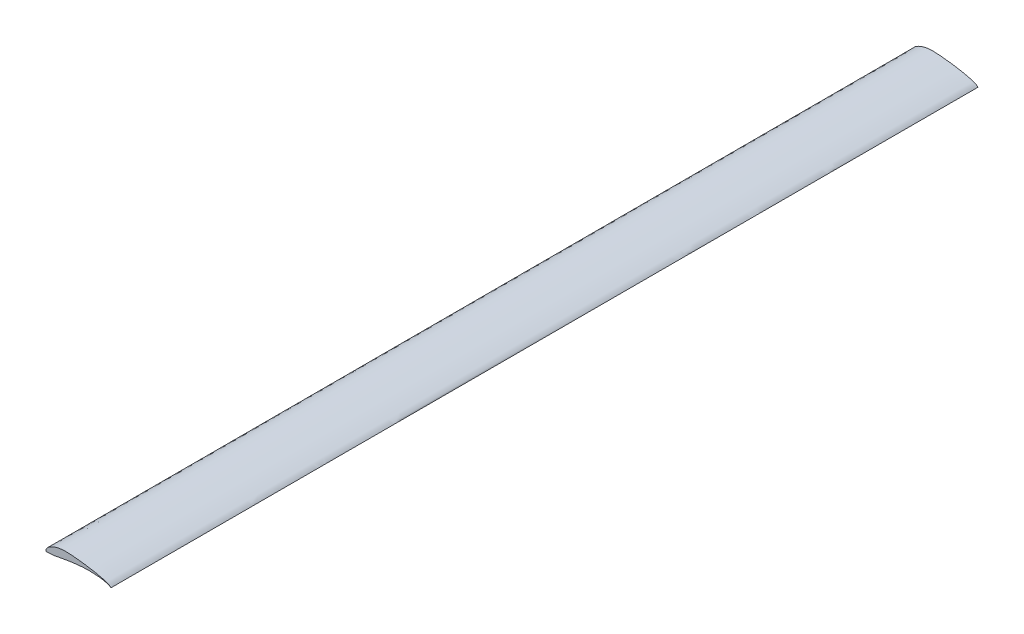
SolidWorks part; units mm, degrees
ref_plane "Front Plane" through (0, 0, 0) normal (0, 0, 1) x (1, 0, 0)
ref_plane "Top Plane" through (0, 0, 0) normal (0, 1, 0) x (1, 0, 0)
ref_plane "Right Plane" through (0, 0, 0) normal (1, 0, 0) x (0, 0, -1)
curve "Curve1"
  spline degree 3 poles (298.8391, 0.7791, 0) (300.272, -0.1937, 0) (299.0156, 0.7424, 0) (298.1815, 1.5608, 0) (296.3296, 3.2701, 0) (294.1447, 5.0885, 0) (291.156, 6.9216, 0) (287.4395, 8.6981, 0) (282.9528, 10.5521, 0) (277.7028, 12.4577, 0) (271.7139, 14.4016, 0) (265.0173, 16.3668, 0) (257.6504, 18.3442, 0) (249.6539, 20.3155, 0) (241.0736, 22.2665, 0) (231.9608, 24.185, 0) (222.371, 26.0611, 0) (212.3603, 27.8718, 0) (201.9917, 29.6144, 0) (191.325, 31.2666, 0) (180.4292, 32.8315, 0) (169.3741, 34.2968, 0) (158.2398, 35.6577, 0) (147.1152, 36.924, 0) (136.0925, 38.0635, 0) (125.2615, 39.0551, 0) (114.6983, 39.843, 0) (104.4633, 40.3849, 0) (94.6135, 40.6189, 0) (85.1993, 40.594, 0) (76.2382, 40.133, 0) (67.7268, 39.1989, 0) (59.6304, 37.8781, 0) (51.9471, 36.167, 0) (44.6848, 34.1605, 0) (37.8742, 31.8941, 0) (31.5442, 29.4209, 0) (25.7343, 26.754, 0) (20.4629, 23.9477, 0) (15.7589, 21.0338, 0) (11.6518, 18.0518, 0) (8.1431, 15.065, 0) (5.2838, 12.0407, 0) (3.0875, 9.0051, 0) (1.4651, 6.0519, 0) (0.4254, 3.2479, 0) (-0.0701, 0.6599, 0) (0.0255, -1.529, 0) (0.5891, -3.5365, 0) (2.6838, -4.5331, 0) (5.5002, -4.6729, 0) (9.3531, -4.8084, 0) (14.1983, -4.5995, 0) (19.9811, -4.2155, 0) (26.6372, -3.6005, 0) (34.0984, -2.7684, 0) (42.3284, -1.7012, 0) (51.3231, -0.2097, 0) (61.1264, 1.6605, 0) (71.7872, 3.696, 0) (83.2535, 5.8452, 0) (95.4531, 8.0188, 0) (108.2966, 10.1354, 0) (121.6843, 12.1242, 0) (135.5008, 13.9123, 0) (149.6219, 15.4476, 0) (163.9141, 16.6612, 0) (178.2341, 17.5215, 0) (192.4322, 17.9944, 0) (206.3544, 18.0542, 0) (219.8454, 17.6966, 0) (232.7507, 16.9302, 0) (244.9151, 15.7648, 0) (256.1938, 14.245, 0) (266.44, 12.4151, 0) (275.5335, 10.3363, 0) (283.3067, 8.1119, 0) (289.6683, 5.7379, 0) (294.2072, 3.5653, 0) (297.5535, 1.5564, 0) (298.8391, 0.7791, 0) (300.272, -0.1937, 0) (299.0156, 0.7424, 0) knots -0.009748 -0.004147 -0.001 0 0.00098 0.003649 0.007483 0.012095 0.017526 0.024052 0.031783 0.040678 0.05071 0.061833 0.073989 0.087118 0.101145 0.115991 0.13157 0.147788 0.164551 0.181758 0.199312 0.217095 0.23499 0.252857 0.270541 0.287887 0.304773 0.321101 0.336806 0.3518 0.366031 0.379616 0.392653 0.40517 0.417172 0.428604 0.439419 0.449597 0.459102 0.467908 0.475988 0.483309 0.489875 0.495803 0.501149 0.505903 0.510047 0.513579 0.516447 0.51935 0.523823 0.529974 0.537716 0.546968 0.557637 0.56962 0.582804 0.597247 0.613135 0.630444 0.649056 0.668822 0.689595 0.71119 0.733427 0.756094 0.778989 0.80189 0.824567 0.846792 0.868338 0.888978 0.908492 0.926659 0.943286 0.958169 0.971136 0.981956 0.990252 0.995853 0.999 1 1.00098 1.003649 1.007483 periodic
sketch "Sketch2" plane through (0, 0, 0) normal (0, 0, 1) x (1, 0, 0)
  spline S0 degree 3 poles (298.8391, 0.7791) (300.272, -0.1937) (299.0156, 0.7424) (298.1815, 1.5608) (296.3296, 3.2701) (294.1447, 5.0885) (291.156, 6.9216) (287.4395, 8.6981) (282.9528, 10.5521) (277.7028, 12.4577) (271.7139, 14.4016) (265.0173, 16.3668) (257.6504, 18.3442) (249.6539, 20.3155) (241.0736, 22.2665) (231.9608, 24.185) (222.371, 26.0611) (212.3603, 27.8718) (201.9917, 29.6144) (191.325, 31.2666) (180.4292, 32.8315) (169.3741, 34.2968) (158.2398, 35.6577) (147.1152, 36.924) (136.0925, 38.0635) (125.2615, 39.0551) (114.6983, 39.843) (104.4633, 40.3849) (94.6135, 40.6189) (85.1993, 40.594) (76.2382, 40.133) (67.7268, 39.1989) (59.6304, 37.8781) (51.9471, 36.167) (44.6848, 34.1605) (37.8742, 31.8941) (31.5442, 29.4209) (25.7343, 26.754) (20.4629, 23.9477) (15.7589, 21.0338) (11.6518, 18.0518) (8.1431, 15.065) (5.2838, 12.0407) (3.0875, 9.0051) (1.4651, 6.0519) (0.4254, 3.2479) (-0.0701, 0.6599) (0.0255, -1.529) (0.5891, -3.5365) (2.6838, -4.5331) (5.5002, -4.6729) (9.3531, -4.8084) (14.1983, -4.5995) (19.9811, -4.2155) (26.6372, -3.6005) (34.0984, -2.7684) (42.3284, -1.7012) (51.3231, -0.2097) (61.1264, 1.6605) (71.7872, 3.696) (83.2535, 5.8452) (95.4531, 8.0188) (108.2966, 10.1354) (121.6843, 12.1242) (135.5008, 13.9123) (149.6219, 15.4476) (163.9141, 16.6612) (178.2341, 17.5215) (192.4322, 17.9944) (206.3544, 18.0542) (219.8454, 17.6966) (232.7507, 16.9302) (244.9151, 15.7648) (256.1938, 14.245) (266.44, 12.4151) (275.5335, 10.3363) (283.3067, 8.1119) (289.6683, 5.7379) (294.2072, 3.5653) (297.5535, 1.5564) (298.8391, 0.7791) (300.272, -0.1937) (299.0156, 0.7424) knots -0.009748 -0.004147 -0.001 0 0.00098 0.003649 0.007483 0.012095 0.017526 0.024052 0.031783 0.040678 0.05071 0.061833 0.073989 0.087118 0.101145 0.115991 0.13157 0.147788 0.164551 0.181758 0.199312 0.217095 0.23499 0.252857 0.270541 0.287887 0.304773 0.321101 0.336806 0.3518 0.366031 0.379616 0.392653 0.40517 0.417172 0.428604 0.439419 0.449597 0.459102 0.467908 0.475988 0.483309 0.489875 0.495803 0.501149 0.505903 0.510047 0.513579 0.516447 0.51935 0.523823 0.529974 0.537716 0.546968 0.557637 0.56962 0.582804 0.597247 0.613135 0.630444 0.649056 0.668822 0.689595 0.71119 0.733427 0.756094 0.778989 0.80189 0.824567 0.846792 0.868338 0.888978 0.908492 0.926659 0.943286 0.958169 0.971136 0.981956 0.990252 0.995853 0.999 1 1.00098 1.003649 1.007483 only from (300, 0) to (300, 0) construction
  spline S1 degree 3 poles (298.8391, 0.7791) (300.272, -0.1937) (299.0156, 0.7424) (298.1815, 1.5608) (296.3296, 3.2701) (294.1447, 5.0885) (291.156, 6.9216) (287.4395, 8.6981) (282.9528, 10.5521) (277.7028, 12.4577) (271.7139, 14.4016) (265.0173, 16.3668) (257.6504, 18.3442) (249.6539, 20.3155) (241.0736, 22.2665) (231.9608, 24.185) (222.371, 26.0611) (212.3603, 27.8718) (201.9917, 29.6144) (191.325, 31.2666) (180.4292, 32.8315) (169.3741, 34.2968) (158.2398, 35.6577) (147.1152, 36.924) (136.0925, 38.0635) (125.2615, 39.0551) (114.6983, 39.843) (104.4633, 40.3849) (94.6135, 40.6189) (85.1993, 40.594) (76.2382, 40.133) (67.7268, 39.1989) (59.6304, 37.8781) (51.9471, 36.167) (44.6848, 34.1605) (37.8742, 31.8941) (31.5442, 29.4209) (25.7343, 26.754) (20.4629, 23.9477) (15.7589, 21.0338) (11.6518, 18.0518) (8.1431, 15.065) (5.2838, 12.0407) (3.0875, 9.0051) (1.4651, 6.0519) (0.4254, 3.2479) (-0.0701, 0.6599) (0.0255, -1.529) (0.5891, -3.5365) (2.6838, -4.5331) (5.5002, -4.6729) (9.3531, -4.8084) (14.1983, -4.5995) (19.9811, -4.2155) (26.6372, -3.6005) (34.0984, -2.7684) (42.3284, -1.7012) (51.3231, -0.2097) (61.1264, 1.6605) (71.7872, 3.696) (83.2535, 5.8452) (95.4531, 8.0188) (108.2966, 10.1354) (121.6843, 12.1242) (135.5008, 13.9123) (149.6219, 15.4476) (163.9141, 16.6612) (178.2341, 17.5215) (192.4322, 17.9944) (206.3544, 18.0542) (219.8454, 17.6966) (232.7507, 16.9302) (244.9151, 15.7648) (256.1938, 14.245) (266.44, 12.4151) (275.5335, 10.3363) (283.3067, 8.1119) (289.6683, 5.7379) (294.2072, 3.5653) (297.5535, 1.5564) (298.8391, 0.7791) (300.272, -0.1937) (299.0156, 0.7424) knots -0.009748 -0.004147 -0.001 0 0.00098 0.003649 0.007483 0.012095 0.017526 0.024052 0.031783 0.040678 0.05071 0.061833 0.073989 0.087118 0.101145 0.115991 0.13157 0.147788 0.164551 0.181758 0.199312 0.217095 0.23499 0.252857 0.270541 0.287887 0.304773 0.321101 0.336806 0.3518 0.366031 0.379616 0.392653 0.40517 0.417172 0.428604 0.439419 0.449597 0.459102 0.467908 0.475988 0.483309 0.489875 0.495803 0.501149 0.505903 0.510047 0.513579 0.516447 0.51935 0.523823 0.529974 0.537716 0.546968 0.557637 0.56962 0.582804 0.597247 0.613135 0.630444 0.649056 0.668822 0.689595 0.71119 0.733427 0.756094 0.778989 0.80189 0.824567 0.846792 0.868338 0.888978 0.908492 0.926659 0.943286 0.958169 0.971136 0.981956 0.990252 0.995853 0.999 1 1.00098 1.003649 1.007483 only from (300, 0) to (300, 0)
extrude "Boss-Extrude2" add sketch "Sketch2" along normal blind 2000 and the other way blind 2000 contours S1
